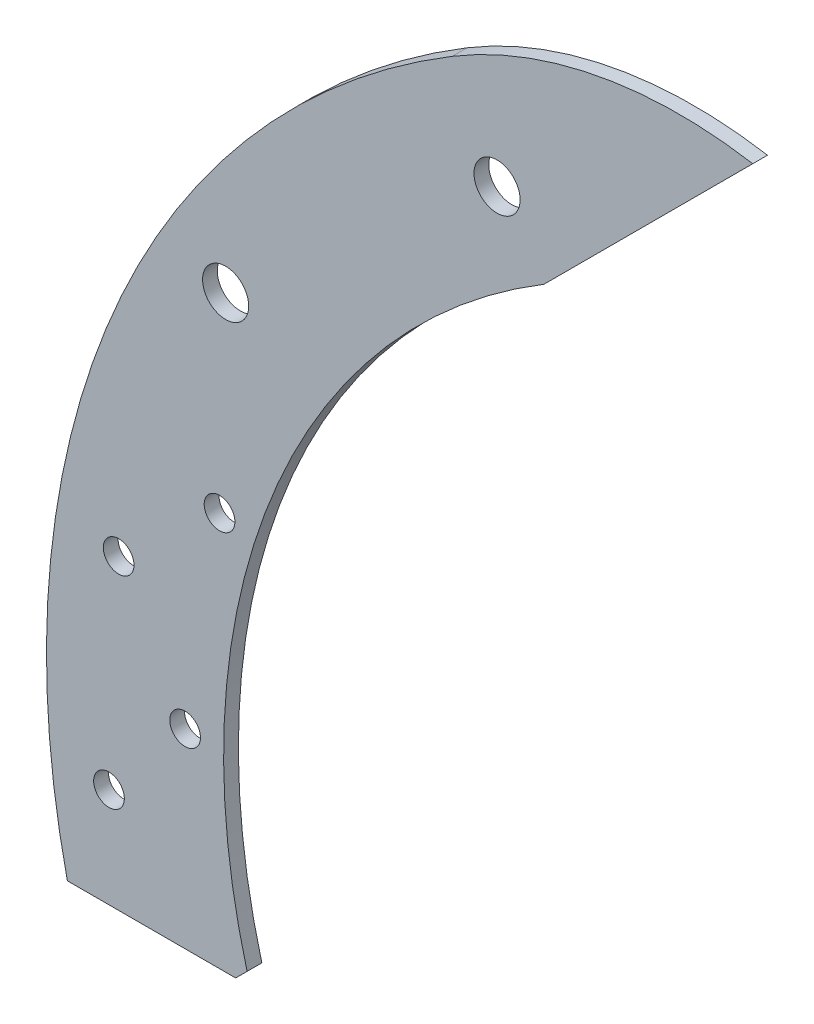
SolidWorks part; units mm, degrees
ref_plane "Front Plane" through (0, 0, 0) normal (0, 0, 1) x (1, 0, 0)
ref_plane "Top Plane" through (0, 0, 0) normal (0, 1, 0) x (1, 0, 0)
ref_plane "Right Plane" through (0, 0, 0) normal (1, 0, 0) x (0, 0, -1)
sketch "Sketch1" plane through (0, 0, 0) normal (0, 0, 1) x (1, 0, 0)
  line L0 (99.8644, -36.5125) -> (-240.4371, -36.5125) construction
  line L1 (-138.956, -36.5125) -> (-175.1568, -36.5125)
  line L2 (-136.5058, -34.0622) -> (-138.956, -36.5125)
  line L3 (-72.6557, 125.8435) -> (-27.7544, 170.7447)
  circle A0 centre (0, 0) radius 36.5125 construction
  arc A5 (-136.5058, -34.0622) -> (-72.6557, 125.8435) centre (1.3579, 3.5895) cw
  arc A6 (-175.1568, -36.5125) -> (-92.3875, 158.4359) centre (1.3579, 3.5895) cw
  arc A8 (-92.3875, 158.4359) -> (-27.7544, 170.7447) centre (-43.5299, 77.7341) cw
  dimension "D1" = 3.5895
  dimension "D3" = 73.025
  dimension "D4" = 142.9127
  dimension "D5" = 38.1
  dimension "D6" = 94.339
  dimension "D2" = 1.3579
  dimension "D7" = 63.5
  dimension "D8" = 135
  dimension "D9" = 44.8878
  dimension "D10" = 45
  dimension "D11" = 137.8636
extrude "Boss-Extrude1" add sketch "Sketch1" along normal blind 3.175
ref_axis "Axis1" through (0, 0, 0) along (0, 0, 1)
sketch "Sketch2" plane through (0, 0, 3.175) normal (0, 0, 1) x (1, 0, 0)
  circle A0 centre (-142.4272, 48.3479) radius 3.302 construction
  circle A1 centre (-149.8374, 4.445) radius 3.302 construction
  circle A2 centre (-142.4272, 48.3479) radius 3.302
  circle A3 centre (-149.8374, 4.445) radius 3.302
extrude "Cut-Extrude1" cut sketch "Sketch2" against normal up to surface (3.175 mm away) up to face at (-117.1327, 62.9696, 0)
sketch "Sketch4" plane through (0, 0, 3.175) normal (0, 0, 1) x (1, 0, 0)
  line L0 (1.3579, 3.5895) -> (-1.7338, -0.0635) construction
  line L1 (-150.6574, -36.5125) -> (-175.1568, -36.5125) construction
  line L2 (1.3579, 3.5895) -> (-1.9604, -4.6358) construction
  line L3 (-152.0013, 1.6278) -> (-143.5465, 51.7193) construction
  line L4 (-147.7739, 26.6735) -> (-164.1258, 29.4335) construction
  arc A0 (-142.4272, 48.3479) -> (-149.8374, 4.445) centre (-0.188, 1.763) ccw construction
  arc A1 (-72.6557, 125.8435) -> (-136.5058, -34.0622) centre (1.3579, 3.5895) ccw construction
  arc A2 (-78.2349, 136.4933) -> (-153.9562, -36.5125) centre (-1.7338, -0.0635) ccw construction
  arc A3 (-78.2349, 136.4933) -> (-153.9562, -36.5125) centre (-1.7338, -0.0635) ccw construction
  arc A4 (-72.6557, 125.8435) -> (-136.5058, -34.0622) centre (1.3579, 3.5895) ccw construction
  arc A5 (-92.3875, 158.4359) -> (-175.1568, -36.5125) centre (1.3579, 3.5895) ccw construction
  arc A6 (-92.3875, 158.4359) -> (-175.1568, -36.5125) centre (1.3579, 3.5895) ccw construction
  arc A7 (-81.4492, 125.0117) -> (-150.6574, -36.5125) centre (-1.9604, -4.6358) ccw construction
  arc A8 (-81.4492, 125.0117) -> (-150.6574, -36.5125) centre (-1.9604, -4.6358) ccw construction
  arc A9 (-162.9071, -36.5125) -> (-166.2054, -15.0736) centre (-0.3012, -0.5231) cw construction
  arc A10 (-166.2054, -15.0736) -> (-164.1258, 29.4335) centre (-0.3012, -0.5231) cw construction
  circle A11 centre (-164.1258, 29.4335) radius 3.302
  circle A12 centre (-166.2054, -15.0736) radius 3.302
  point P25 (-147.7739, 26.6735)
  dimension "D2" = 6.604
  dimension "D1" = 50.8
extrude "Cut-Extrude2" cut sketch "Sketch4" against normal up to surface (3.175 mm away) up to face at (-153.1394, 4.445, 0)
hole_wizard "25/64 (0.39063) Diameter Hole1" positions "Sketch5" profile "Sketch6" hole size "25/64" standard "ANSI Inch" end condition through all
sketch "Sketch5" plane through (0, 0, 3.175) normal (0, 0, 1) x (1, 0, 0)
  line L0 (-82.7471, 138.9947) -> (-141.1196, 90.0143) construction
  line L3 (-72.6557, 125.8435) -> (-27.7544, 170.7447) construction
  point P0 (-82.7471, 138.9947)
  point P2 (-141.1196, 90.0143)
  point P13 (-126.8373, 93.6795)
  point P14 (-73.9367, 149.5825)
  point P15 (-72.1523, 146.0572)
  dimension "D1" = 76.2
  dimension "D2" = 5
  dimension "D3" = 63.5
  dimension "D4" = 31.75
sketch "Sketch6" plane through (-82.7471, 138.9947, 3.175) normal (1, 0, 0) x (0, -1, 0)
  line L0 (0, 0) -> (0, 3.175)
  line L1 (0, 3.175) -> (4.961, 3.175)
  line L2 (4.961, 3.175) -> (4.961, 0)
  line L5 (4.961, 0) -> (0, 0)
  line L11 (0, -6.35) -> (0, 107.95) construction
  dimension "Thru Hole Dia." = 9.922
  dimension "Thru Hole Depth" = 3.175
